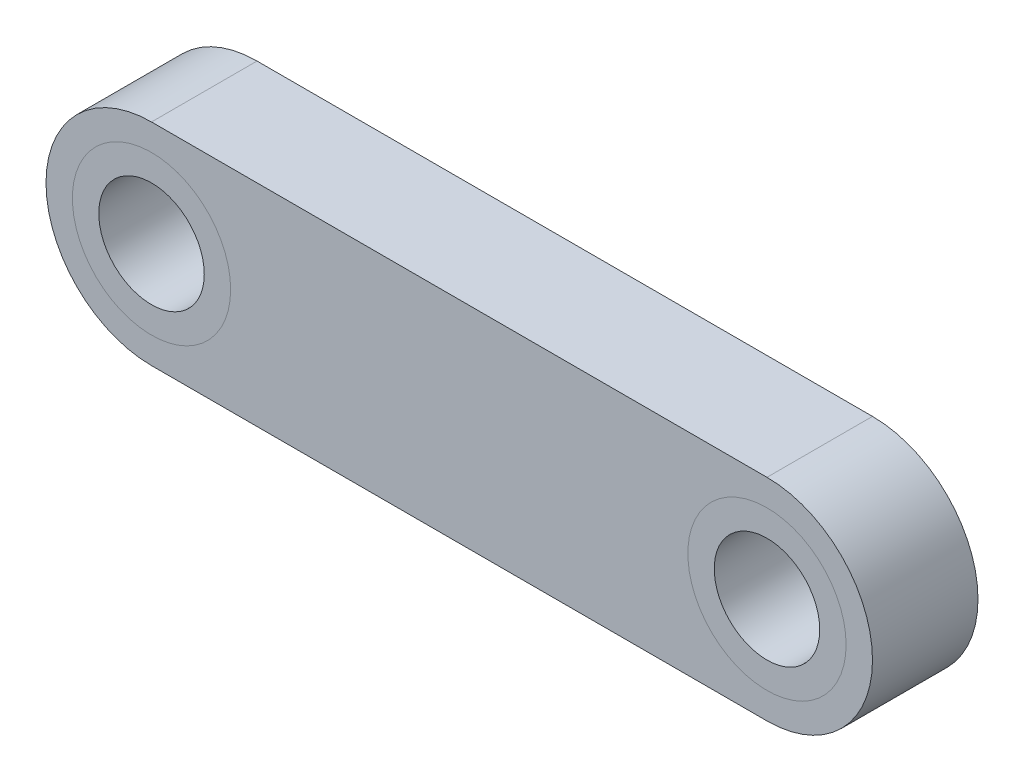
SolidWorks part; units mm, degrees
ref_plane "Front Plane" through (0, 0, 0) normal (0, 0, 1) x (1, 0, 0)
ref_plane "Top Plane" through (0, 0, 0) normal (0, 1, 0) x (1, 0, 0)
ref_plane "Right Plane" through (0, 0, 0) normal (1, 0, 0) x (0, 0, -1)
sketch "Sketch1" plane through (0, 0, 0) normal (0, 0, 1) x (1, 0, 0)
  line L0 (-17.5, 0) -> (17.5, 0) construction
  line L1 (-17.5, 6) -> (17.5, 6)
  line L2 (-17.5, -6) -> (17.5, -6)
  line L3 (0, 0) -> (0, -50000) construction
  arc A0 (-17.5, 6) -> (-17.5, -6) centre (-17.5, 0) ccw
  arc A1 (17.5, -6) -> (17.5, 6) centre (17.5, 0) ccw
  circle A2 centre (-17.5, 0) radius 4.5
  circle A3 centre (-17.5, 0) radius 3
  circle A4 centre (17.5, 0) radius 3
  circle A5 centre (17.5, 0) radius 4.5
  point P2 (0, 0)
  dimension "D2" = 6
  dimension "D3" = 6
  dimension "9" = 9
  dimension "D1" = 35
extrude "Boss-Extrude1" add sketch "Sketch1" along normal mid plane 6 contours L2 A1 L1 A0 A2 A5 region at (0, 0, 0)
extrude "Boss-Extrude2" add sketch "Sketch1<3>" along normal mid plane 6 separate body contours A2 A3 | A5 A4 region at (-21.8727, 0, 0) region at (13.1273, 0, 0)
sketch "Sketch1<3>" plane through (0, 0, 0) normal (0, 0, 1) x (1, 0, 0) same geometry as "Sketch1"
